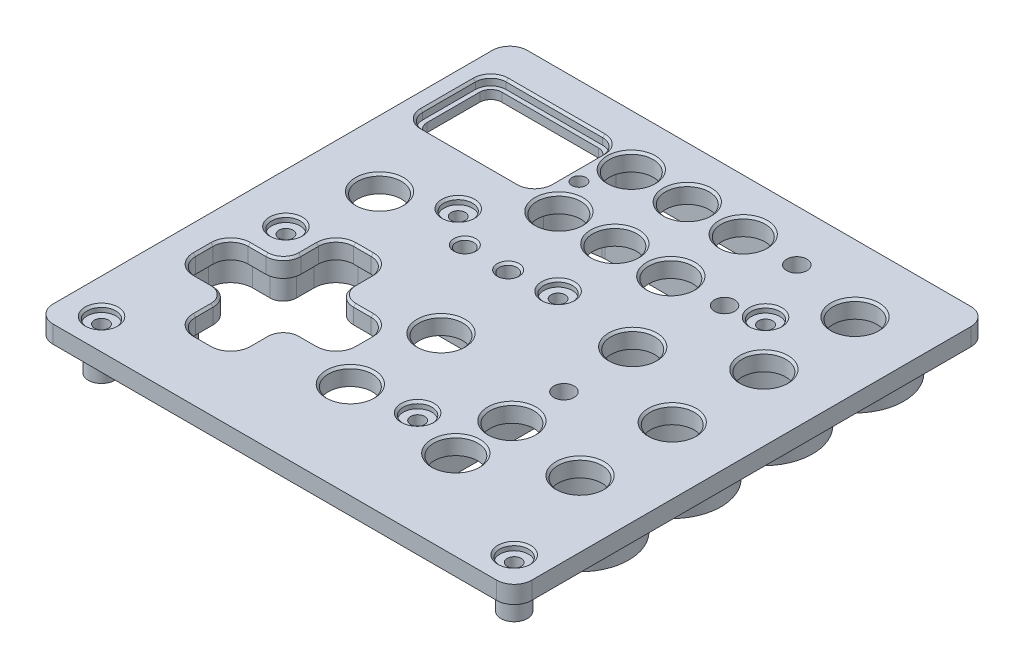
SolidWorks part; units mm, degrees
other "Markup1"
sketch "Sketch10" plane through (-33.0518, -8.9554, -52.6589) normal (-0.1076, -0.9941, -0.0133) x (0.4564, -0.0613, 0.8876)
ref_plane "Front Plane" through (0, 0, 0) normal (0, 0, 1) x (1, 0, 0)
ref_plane "Top Plane" through (0, 0, 0) normal (0, 1, 0) x (1, 0, 0)
ref_plane "Right Plane" through (0, 0, 0) normal (1, 0, 0) x (0, 0, -1)
sketch "Sketch1" plane through (0, 0, 0) normal (0, 1, 0) x (1, 0, 0)
  line L0 (32.6312, 56.5) -> (133.6312, 56.5)
  line L7 (137.6312, -47.5) -> (137.6312, 52.5)
  line L28 (28.6312, 52.5) -> (28.6312, -47.5)
  line L30 (32.6312, -51.5) -> (133.6312, -51.5)
  arc A0 (28.6312, -47.5) -> (32.6312, -51.5) centre (32.6312, -47.5) ccw
  arc A1 (133.6312, -51.5) -> (137.6312, -47.5) centre (133.6312, -47.5) ccw
  arc A2 (137.6312, 52.5) -> (133.6312, 56.5) centre (133.6312, 52.5) ccw
  arc A3 (32.6312, 56.5) -> (28.6312, 52.5) centre (32.6312, 52.5) ccw
  dimension "D2" = 4
extrude "Boss-Extrude1" add sketch "Sketch1" along normal blind 4
sketch "Sketch3" plane through (0, 4, 0) normal (0, 1, 0) x (1, 0, 0)
  line L44 (50.9951, -1.4499) -> (54.9951, -1.4499)
  line L45 (58.9951, -5.4499) -> (58.9951, -9.4499)
  line L46 (62.9951, -13.4499) -> (66.9951, -13.4499)
  line L47 (70.9951, -17.4499) -> (70.9951, -21.4499)
  line L48 (66.9951, -25.4499) -> (62.9951, -25.4499)
  line L49 (58.9951, -29.4499) -> (58.9951, -33.4499)
  line L50 (54.9951, -37.4499) -> (50.9951, -37.4499)
  line L51 (46.9951, -33.4499) -> (46.9951, -29.4499)
  line L52 (42.9951, -25.4499) -> (38.9951, -25.4499)
  line L53 (34.9951, -21.4499) -> (34.9951, -17.4499)
  line L54 (38.9951, -13.4499) -> (42.9951, -13.4499)
  line L55 (46.9951, -9.4499) -> (46.9951, -5.4499)
  circle A2 centre (122.5061, 41.25) radius 5
  circle A3 centre (122.5061, 20.5) radius 5
  circle A4 centre (122.5061, -0.375) radius 5
  circle A5 centre (122.5061, -21.375) radius 5
  circle A6 centre (103.9561, -18.35) radius 5
  circle A7 centre (103.1311, 10) radius 5
  circle A8 centre (78.5811, -9.125) radius 5
  circle A9 centre (78.3063, -29.5) radius 5
  circle A10 centre (43.6312, 11.8249) radius 5
  circle A11 centre (68.0062, 28.3001) radius 5
  circle A12 centre (80.7562, 28.3001) radius 5
  circle A13 centre (93.5062, 28.3001) radius 5
  circle A14 centre (93.5062, 44.8001) radius 5
  circle A15 centre (80.7562, 44.8001) radius 5
  circle A16 centre (68.0062, 44.8001) radius 5
  circle A17 centre (103.9561, -31.125) radius 5
  circle A18 centre (63.8812, 11.0001) radius 2
  circle A19 centre (73.7562, 10.9999) radius 2
  arc A20 (58.9951, -29.4499) -> (62.9951, -25.4499) centre (62.9951, -29.4499) cw
  arc A21 (62.9951, -13.4499) -> (58.9951, -9.4499) centre (62.9951, -9.4499) cw
  arc A22 (46.9951, -9.4499) -> (42.9951, -13.4499) centre (42.9951, -9.4499) cw
  arc A23 (46.9951, -29.4499) -> (42.9951, -25.4499) centre (42.9951, -29.4499) ccw
  arc A24 (70.9951, -17.4499) -> (66.9951, -13.4499) centre (66.9951, -17.4499) ccw
  arc A25 (58.9951, -5.4499) -> (54.9951, -1.4499) centre (54.9951, -5.4499) ccw
  arc A26 (50.9951, -1.4499) -> (46.9951, -5.4499) centre (50.9951, -5.4499) ccw
  arc A27 (38.9951, -13.4499) -> (34.9951, -17.4499) centre (38.9951, -17.4499) ccw
  arc A28 (34.9951, -21.4499) -> (38.9951, -25.4499) centre (38.9951, -21.4499) ccw
  arc A29 (46.9951, -33.4499) -> (50.9951, -37.4499) centre (50.9951, -33.4499) ccw
  arc A30 (54.9951, -37.4499) -> (58.9951, -33.4499) centre (54.9951, -33.4499) ccw
  arc A31 (66.9951, -25.4499) -> (70.9951, -21.4499) centre (66.9951, -21.4499) ccw
  circle A32 centre (105.6344, 44.8749) radius 2.3
  circle A33 centre (105.4147, 28.6249) radius 2.3
  circle A34 centre (104.1313, -6.6735) radius 2.3
  point P54 (58.9951, -13.4499)
extrude "Cut-Extrude2" cut sketch "Sketch3" against normal through all
sketch "Sketch11" plane through (0, 4, 0) normal (0, 1, 0) x (1, 0, 0)
  line L0 (61.4355, 44.8615) -> (61.4355, 32.8615)
  line L4 (32.4355, 32.8615) -> (32.4355, 44.8615)
  line L6 (35.9355, 48.3615) -> (57.9355, 48.3615)
  line L8 (61.4355, 44.8615) -> (61.4355, 32.8615)
  line L9 (57.9355, 29.3615) -> (35.9355, 29.3615)
  line L10 (32.4355, 32.8615) -> (32.4355, 44.8615)
  line L11 (35.9355, 48.3615) -> (57.9355, 48.3615)
  line L13 (57.9355, 29.3615) -> (35.9355, 29.3615)
  arc A0 (57.9355, 29.3615) -> (61.4355, 32.8615) centre (57.9355, 32.8615) ccw
  arc A1 (32.4355, 32.8615) -> (35.9355, 29.3615) centre (35.9355, 32.8615) ccw
  arc A2 (35.9355, 48.3615) -> (32.4355, 44.8615) centre (35.9355, 44.8615) ccw
  arc A3 (61.4355, 44.8615) -> (57.9355, 48.3615) centre (57.9355, 44.8615) ccw
  arc A4 (57.9355, 29.3615) -> (61.4355, 32.8615) centre (57.9355, 32.8615) ccw
  arc A5 (32.4355, 32.8615) -> (35.9355, 29.3615) centre (35.9355, 32.8615) ccw
  arc A6 (35.9355, 48.3615) -> (32.4355, 44.8615) centre (35.9355, 44.8615) ccw
  arc A7 (61.4355, 44.8615) -> (57.9355, 48.3615) centre (57.9355, 44.8615) ccw
extrude "Cut-Extrude8" cut sketch "Sketch11" against normal blind 2
sketch "Sketch12" plane through (0, 2, 0) normal (0, 1, 0) x (1, 0, 0)
  line L4 (57.9355, 47.3615) -> (35.9355, 47.3615)
  line L5 (57.9355, 47.3615) -> (35.9355, 47.3615)
  line L6 (33.4355, 44.8615) -> (33.4355, 32.8615)
  line L7 (33.4355, 44.8615) -> (33.4355, 32.8615)
  line L8 (35.9355, 30.3615) -> (57.9355, 30.3615)
  line L9 (35.9355, 30.3615) -> (57.9355, 30.3615)
  line L10 (60.4355, 32.8615) -> (60.4355, 44.8615)
  line L11 (60.4355, 32.8615) -> (60.4355, 44.8615)
  arc A4 (60.4355, 44.8615) -> (57.9355, 47.3615) centre (57.9355, 44.8615) ccw
  arc A5 (60.4355, 44.8615) -> (57.9355, 47.3615) centre (57.9355, 44.8615) ccw
  arc A6 (35.9355, 47.3615) -> (33.4355, 44.8615) centre (35.9355, 44.8615) ccw
  arc A7 (35.9355, 47.3615) -> (33.4355, 44.8615) centre (35.9355, 44.8615) ccw
  arc A8 (33.4355, 32.8615) -> (35.9355, 30.3615) centre (35.9355, 32.8615) ccw
  arc A9 (33.4355, 32.8615) -> (35.9355, 30.3615) centre (35.9355, 32.8615) ccw
  arc A10 (57.9355, 30.3615) -> (60.4355, 32.8615) centre (57.9355, 32.8615) ccw
  arc A11 (57.9355, 30.3615) -> (60.4355, 32.8615) centre (57.9355, 32.8615) ccw
  dimension "D1" = 1
extrude "Cut-Extrude9" cut sketch "Sketch12" against normal through all
sketch "Sketch13" plane through (0, 0, 0) normal (0, -1, 0) x (1, 0, 0)
  line L0 (133.6312, -52.5) -> (28.6312, -52.5) construction
  line L2 (112.3813, -52.5) -> (112.3813, -45.8325)
  line L4 (61.3813, -52.5) -> (61.3813, -21.5)
  line L5 (68.0062, -22.3001) -> (106.5062, -22.3001)
  line L7 (68.0062, -51.3001) -> (106.5062, -51.3001)
  line L8 (110.5062, -47.3001) -> (110.5062, -42.8001)
  line L10 (68.0062, -38.8001) -> (106.5062, -38.8001)
  line L12 (110.5062, -34.3001) -> (110.5062, -26.3001)
  line L14 (92.0062, -10.073) -> (92.0062, -16.5)
  line L16 (96.9561, 31.125) -> (96.9561, 6.3677)
  line L17 (110.9561, 6.3677) -> (110.9561, 31.125)
  line L18 (94.9561, 31.125) -> (94.9561, 6.3677)
  line L20 (112.9561, 27.1102) -> (112.9561, 31.125)
  line L22 (112.9561, 6.3677) -> (112.9561, 31.125) construction
  line L58 (49.0951, -3.4501) -> (56.6951, -3.4501)
  line L64 (51.4145, 42.1499) -> (49.0951, 42.1499)
  line L65 (42.0951, 35.1499) -> (42.0951, 31.1499)
  line L66 (41.0951, 30.1499) -> (37.0951, 30.1499)
  line L67 (30.0951, 23.1499) -> (30.0951, 15.5499)
  line L68 (37.0951, 8.5499) -> (41.0951, 8.5499)
  line L69 (42.0951, 7.5499) -> (42.0951, 3.5499)
  line L78 (87, 41.2148) -> (87, 1.6203)
  line L80 (87, 41.2148) -> (81.1395, 41.2148)
  line L90 (80.1354, -3.1952) -> (60.3806, -3.1952)
  line L91 (60.3806, -3.1952) -> (56.6951, -3.4501)
  line L92 (81.1395, 41.2148) -> (80.9453, 41.2148)
  line L98 (78.4256, -1.1952) -> (60.3115, -1.1952)
  line L99 (60.3115, -1.1952) -> (56.626, -1.4501)
  line L100 (49.0951, -1.4501) -> (56.626, -1.4501)
  line L101 (44.0951, 7.5499) -> (44.0951, 3.5499)
  line L102 (37.0951, 10.5499) -> (41.0951, 10.5499)
  line L103 (32.0951, 23.1499) -> (32.0951, 15.5499)
  line L104 (41.0951, 28.1499) -> (37.0951, 28.1499)
  line L105 (44.0951, 35.1499) -> (44.0951, 31.1499)
  line L106 (56.6951, 40.1499) -> (49.0951, 40.1499)
  line L112 (88.0062, -20.5) -> (61.3813, -20.5)
  line L113 (61.3813, -20.5) -> (61.3813, -21.5)
  line L114 (110.5062, -34.3001) -> (110.5062, -35.3001)
  line L115 (110.5062, -35.3001) -> (71.526, -35.3001)
  line L117 (72.1395, 36.8974) -> (59.4553, 39.319) construction
  line L118 (81.8089, 36.8974) -> (72.1395, 36.8974) construction
  line L119 (72.3287, 38.8974) -> (60.1904, 41.2148) construction
  line L120 (79.8089, 38.8974) -> (72.3287, 38.8974) construction
  line L122 (85, 39.2148) -> (85, 0.6001) construction
  line L123 (85, 39.2148) -> (81.8089, 39.2148) construction
  line L124 (81.8089, 39.2148) -> (81.8089, 36.8974) construction
  line L126 (81.8089, 39.2148) -> (81.8089, 39.2148) construction
  line L127 (85, 0.6001) -> (78.6937, 0.6001) construction
  line L128 (85, 0.6001) -> (85, 0.6001) construction
  line L129 (85, 4.6001) -> (85, 35.9119)
  line L130 (85, 4.6001) -> (85, 4.3183)
  line L135 (61.3813, -52.5) -> (112.3813, -52.5)
  line L136 (56.6951, 42.1499) -> (49.0951, 42.1499) construction
  line L137 (81.7885, 39.1911) -> (60.1254, 39.1911)
  line L138 (79.8089, 41.2148) -> (79.8089, 38.8974) construction
  line L139 (60.7768, 41.1028) -> (72.9994, 41.1028)
  line L143 (81.1395, 41.2148) -> (79.8089, 41.2148) construction
  line L144 (81.2306, -3.0424) -> (84.0953, -2.2268)
  line L145 (82.4501, -0.032) -> (82.3087, -0.1438)
  line L146 (80.3612, -0.9707) -> (78.9594, -1.1595)
  line L147 (78.6937, -1.1952) -> (60.3115, -1.1952) construction
  line L148 (78.6937, 0.6001) -> (78.6937, -1.1952) construction
  line L149 (85.6449, -1.3999) -> (80.6937, -1.3999) construction
  line L150 (87, -1.3999) -> (85.6449, -1.3999) construction
  line L151 (80.6937, -1.3999) -> (80.6937, -3.1952) construction
  line L152 (80.6937, -3.1952) -> (60.3806, -3.1952) construction
  line L153 (87, 41.2148) -> (87, -1.3999) construction
  line L154 (68.272, -34.8415) -> (70.9104, -35.2525)
  arc A5 (68.0062, -38.8001) -> (62.3939, -46.9221) centre (68.0062, -44.8001) ccw
  arc A7 (68.0062, -51.3001) -> (62.3939, -46.9221) centre (68.0062, -45.5139) cw
  circle A8 centre (122.5061, -41.25) radius 10
  circle A9 centre (122.5061, -20.5) radius 10
  circle A10 centre (122.5061, 0.4031) radius 10
  circle A11 centre (103.1311, -10) radius 10
  circle A12 centre (122.5061, 21.375) radius 10
  arc A15 (130.5136, 13.6804) -> (112.9561, 27.1102) centre (122.506, 21.4034) ccw
  arc A16 (105.5959, 0.8487) -> (101.7697, 1.0416) centre (103.1311, -10) ccw
  arc A20 (130.5579, -7.2744) -> (130.5137, 8.1267) centre (122.5061, 0.4031) ccw
  arc A21 (130.6014, -28.1034) -> (130.5579, -12.795) centre (122.5062, -20.4722) ccw
  arc A25 (112.3813, -45.8325) -> (130.6014, -33.5909) centre (122.5062, -41.2222) ccw
  arc A26 (110.9561, 31.125) -> (96.9561, 31.125) centre (103.9561, 31.125) ccw
  arc A28 (96.9561, 6.3677) -> (97.7122, 3.2032) centre (103.9561, 6.3677) ccw
  arc A29 (112.9561, 31.125) -> (94.9561, 31.125) centre (103.9561, 31.125) ccw
  arc A30 (94.9561, 6.3677) -> (95.8988, 2.3578) centre (103.9561, 6.3677) ccw
  arc A34 (109.8501, 2.5914) -> (110.9561, 6.3677) centre (103.9561, 6.3677) ccw
  arc A35 (94.9561, 6.3677) -> (112.9561, 6.3677) centre (103.9561, 6.3677) ccw construction
  arc A36 (95.1775, -2.2212) -> (92.0062, -10.073) centre (103.1311, -10) ccw
  arc A37 (96.9561, 6.3677) -> (110.9561, 6.3677) centre (103.9561, 6.3677) ccw construction
  arc A76 (42.0951, 3.5499) -> (49.0951, -3.4501) centre (49.0951, 3.5499) ccw
  arc A82 (59.7699, 41.4384) -> (56.6951, 42.1499) centre (56.6951, 35.1499) ccw
  arc A83 (49.0951, 42.1499) -> (42.0951, 35.1499) centre (49.0951, 35.1499) ccw
  arc A84 (41.0951, 30.1499) -> (42.0951, 31.1499) centre (41.0951, 31.1499) ccw
  arc A85 (37.0951, 30.1499) -> (30.0951, 23.1499) centre (37.0951, 23.1499) ccw
  arc A86 (30.0951, 15.5499) -> (37.0951, 8.5499) centre (37.0951, 15.5499) ccw
  arc A87 (42.0951, 7.5499) -> (41.0951, 8.5499) centre (41.0951, 7.5499) ccw
  arc A90 (44.0951, 3.5499) -> (49.0951, -1.4501) centre (49.0951, 3.5499) ccw
  arc A91 (44.0951, 7.5499) -> (41.0951, 10.5499) centre (41.0951, 7.5499) ccw
  arc A92 (32.0951, 15.5499) -> (37.0951, 10.5499) centre (37.0951, 15.5499) ccw
  arc A93 (37.0951, 28.1499) -> (32.0951, 23.1499) centre (37.0951, 23.1499) ccw
  arc A94 (41.0951, 28.1499) -> (44.0951, 31.1499) centre (41.0951, 31.1499) ccw
  arc A95 (49.0951, 40.1499) -> (44.0951, 35.1499) centre (49.0951, 35.1499) ccw
  arc A96 (59.0175, 39.5778) -> (56.6951, 40.1499) centre (56.6951, 35.1499) ccw
  arc A97 (88.0062, -20.5) -> (92.0062, -16.5) centre (88.0062, -16.5) ccw
  arc A98 (130.5136, 13.6804) -> (130.5137, 8.1267) centre (133.3928, 10.9036) ccw
  arc A99 (130.6014, -28.1034) -> (130.6014, -33.5909) centre (133.512, -30.8472) ccw
  arc A100 (130.5579, -7.2744) -> (130.5579, -12.795) centre (133.4528, -10.0347) ccw
  arc A101 (105.5959, 0.8487) -> (109.8501, 2.5914) centre (106.4821, 4.7493) ccw
  arc A102 (101.7697, 1.0416) -> (97.7122, 3.2032) centre (101.2802, 5.0115) cw
  arc A103 (106.5062, -51.3001) -> (110.5062, -47.3001) centre (106.5062, -47.3001) ccw
  arc A104 (106.5062, -38.8001) -> (110.5062, -42.8001) centre (106.5062, -42.8001) cw
  arc A105 (106.5062, -22.3001) -> (110.5062, -26.3001) centre (106.5062, -26.3001) cw
  arc A107 (59.4553, 39.319) -> (56.6951, 40.1499) centre (56.6951, 35.1499) ccw construction
  arc A108 (59.0175, 39.5778) -> (60.1254, 39.1911) centre (60.8755, 43.1201) ccw
  arc A109 (60.1904, 41.2148) -> (56.6951, 42.1499) centre (56.6951, 35.1499) ccw construction
  arc A110 (59.7699, 41.4384) -> (60.7768, 41.1028) centre (61.527, 45.0318) ccw
  arc A112 (95.8988, 2.3578) -> (95.1775, -2.2212) centre (92.3178, 0.5756) cw
  arc A113 (85, 35.9119) -> (81.7885, 39.1911) centre (83.5458, 37.6999) ccw
  arc A115 (83.8131, 0.6711) -> (85.1693, 3.167) centre (83.2539, 2.5914) ccw
  arc A116 (85.1693, 3.167) -> (85, 4.3183) centre (89, 4.3183) cw
  arc A117 (56.6951, 42.1499) -> (55.6799, 42.0189) centre (56.6951, 38.1499) ccw
  arc A118 (51.4145, 42.1499) -> (52.8417, 41.8866) centre (51.4145, 38.1499) cw
  arc A119 (52.8417, 41.8866) -> (55.6799, 42.0189) centre (54.1092, 45.2051) ccw
  arc A120 (74.7448, 40.7019) -> (72.9994, 41.1028) centre (72.9994, 37.1028) ccw
  arc A121 (74.7448, 40.7019) -> (79.0991, 40.7632) centre (76.8609, 45.0653) ccw
  arc A122 (80.9453, 41.2148) -> (79.0991, 40.7632) centre (80.9453, 37.2148) ccw
  arc A123 (78.9594, -1.1595) -> (78.4256, -1.1952) centre (78.4256, 2.8048) cw
  arc A124 (82.3087, -0.1438) -> (80.3612, -0.9707) centre (79.8274, 2.9935) cw
  arc A125 (83.8131, 0.6711) -> (82.4501, -0.032) centre (84.9315, -3.1693) ccw
  arc A126 (81.2306, -3.0424) -> (80.1354, -3.1952) centre (80.1354, 0.8048) cw
  arc A127 (87, 1.6203) -> (84.0953, -2.2268) centre (83, 1.6203) cw
  arc A128 (67.7993, -34.7964) -> (62.3939, -30.4221) centre (68.0062, -29.0139) cw
  arc A129 (68.0062, -22.3001) -> (62.3939, -30.4221) centre (68.0062, -28.3001) ccw
  arc A130 (71.526, -35.3001) -> (70.9104, -35.2525) centre (71.526, -31.3001) cw
  arc A131 (68.272, -34.8415) -> (67.7993, -34.7964) centre (67.6564, -38.7939) ccw
  point P139 (56.6951, 3.5499)
  point P140 (63.6951, 3.5499)
  point P144 (68.6951, 8.5499)
  point P145 (68.6951, 15.5499)
  point P146 (75.6951, 15.5499)
  point P153 (63.6951, 35.1499)
  dimension "D3" = 4
  dimension "D1" = 4
  dimension "D4" = 4
  dimension "D5" = 4
  dimension "D6" = 4
  dimension "D7" = 4
  dimension "D8" = 4
  dimension "D9" = 4
  dimension "D10" = 4
  dimension "D11" = 4
  dimension "D12" = 4
  dimension "D13" = 4
  dimension "D14" = 4
  dimension "D15" = 4
  dimension "D16" = 4
  dimension "D17" = 4
  dimension "D2" = 51
extrude "Boss-Extrude2" add sketch "Sketch13" along normal blind 7.1
sketch "Sketch14" plane through (0, -7.1, 0) normal (0, -1, 0) x (1, 0, 0)
  line L0 (110.9561, 31.125) -> (110.9561, 40.2144)
  line L5 (110.9561, 40.2144) -> (106.9561, 40.2144)
  line L7 (106.9561, 31.125) -> (110.9561, 31.125)
  line L8 (106.9561, 31.125) -> (96.9561, 31.125)
  line L9 (96.9561, 31.125) -> (96.9561, 40.2144)
  line L10 (96.9561, 40.2144) -> (106.9561, 40.2144)
extrude "Cut-Extrude10" cut sketch "Sketch14" against normal blind 1.5
sketch "Sketch8" plane through (0, 4, 0) normal (0, -1, 0) x (-1, 0, 0)
  circle A0 centre (-36.6312, -44.5) radius 1.6
  circle A1 centre (-91.6312, -27.5) radius 1.6
  circle A2 centre (-39.8812, -5.75) radius 1.6
  circle A3 centre (-56.0062, 17.375) radius 1.6
  circle A4 centre (-64.3812, 36.5) radius 1.6
  circle A5 centre (-83.6312, 12.5) radius 1.6
  circle A6 centre (-112.3812, 31) radius 1.6
  circle A7 centre (-130.6312, -44.5) radius 1.6
extrude "Cut-Extrude7" cut sketch "Sketch8" along normal through all
sketch "Sketch16" plane through (0, 0, 0) normal (0, -1, 0) x (1, 0, 0)
  line L1 (37.0951, 8.5499) -> (41.0951, 8.5499) construction
  line L3 (40.9586, 8.5499) -> (41.0951, 8.5499)
  line L4 (87, 1.6203) -> (87, 41.2148) construction
  line L5 (94.9561, 31.125) -> (94.9561, 6.3677) construction
  line L6 (87, 24.5) -> (87, 30.5)
  line L7 (94.9561, 30.5) -> (94.9561, 24.5)
  line L8 (91.6312, 24.5) -> (87, 24.5)
  line L9 (91.6312, 30.5) -> (87, 30.5)
  line L10 (91.6312, 30.5) -> (94.9561, 30.5)
  line L11 (91.6312, 24.5) -> (94.9561, 24.5)
  circle A0 centre (36.6312, 44.5) radius 3
  arc A1 (40.9586, 8.5499) -> (42.0601, 7.8121) centre (39.8812, 5.75) ccw
  circle A2 centre (56.0062, -17.375) radius 3
  circle A4 centre (130.6312, 44.5) radius 3
  circle A5 centre (83.6312, -12.5) radius 3
  arc A6 (42.0951, 7.5499) -> (41.0951, 8.5499) centre (41.0951, 7.5499) ccw construction
  arc A7 (42.0601, 7.8121) -> (41.0951, 8.5499) centre (41.0951, 7.5499) ccw
fillet "Fillet1" radius 4 1 edges at (110.5062, -3.55, -35.3001)
fillet "Fillet2" radius 4 1 edges at (112.9561, -3.55, 27.1102)
fillet "Fillet5" radius 4 1 edges at (112.3813, -3.55, -45.8325)
sketch "Sketch15" plane through (0, 4, 0) normal (0, 1, 0) x (1, 0, 0)
  circle A0 centre (56.0062, 17.375) radius 3.25
  circle A1 centre (39.8812, -5.75) radius 3.25
  circle A2 centre (36.6312, -44.5) radius 3.25
  circle A3 centre (91.6312, -27.5) radius 3.25
  circle A4 centre (130.6312, -44.5) radius 3.25
  circle A5 centre (112.3812, 31) radius 3.25
  circle A6 centre (83.6312, 12.5) radius 3.25
extrude "Cut-Extrude11" cut sketch "Sketch15" against normal blind 1.5
chamfer "Chamfer1" distance 0.5 angle 45 57 edges at (93.5062, 4, -39.8001) (80.7562, 4, -39.8001) (68.0062, 4, -39.8001) (63.8812, 4, -9.0001) (73.7562, 4, -8.9999) (83.6312, 4, -9.25) (56.0062, 4, -14.125) (43.6312, 4, -6.8249) (39.8812, 4, 9) (36.6312, 4, 47.75) (52.9951, 4, 37.4499) (46.9951, 4, 31.4499) (45.8235, 4, 26.6215) (40.9951, 4, 25.4499) (34.9951, 4, 19.4499) (40.9951, 4, 13.4499) (45.8235, 4, 12.2783) (46.9951, 4, 7.4499) (52.9951, 4, 1.4499) (58.9951, 4, 31.4499) (58.9951, 4, 7.4499) (60.1667, 4, 26.6215) (60.1667, 4, 12.2783) (64.9951, 4, 25.4499) (70.9951, 4, 19.4499) (64.9951, 4, 13.4499) (78.5811, 4, 14.125) (78.3063, 4, 34.5) (130.6312, 4, 47.75) (91.6312, 4, 30.75) (103.9561, 4, 36.125) (103.9561, 4, 23.35) (122.5061, 4, 26.375) (122.5061, 4, 5.375) (103.1311, 4, -5) (122.5061, 4, -15.5) (112.3812, 4, -27.75) (93.5062, 4, -23.3001) (80.7562, 4, -23.3001) (68.0062, 4, -23.3001) (32.4355, 4, -38.8615) (61.4355, 4, -38.8615) (46.9355, 4, -29.3615) (60.4103, 4, -30.3866) (33.4606, 4, -30.3866) (60.4103, 4, -47.3364) (33.4606, 4, -47.3364) (46.9355, 4, -48.3615) (122.5061, 4, -36.25) (36.1667, 4, 24.2783) (48.1667, 4, 36.2783) (36.1667, 4, 14.6215) (57.8235, 4, 36.2783) (48.1667, 4, 2.6215) (69.8235, 4, 24.2783) (57.8235, 4, 2.6215) (69.8235, 4, 14.6215)
fillet "Fillet10" radius 3 1 edges at (87, -3.55, 41.2148)
extrude "Boss-Extrude4" add sketch "Sketch16" along normal up to surface (7.1 mm away) up to face at (112.3812, -7.1, -32.6)
sketch "Sketch17" plane through (0, 0, 0) normal (0, 1, 0) x (1, 0, 0)
  circle A0 centre (36.6312, -44.5) radius 1.6
  circle A1 centre (39.8812, -5.75) radius 1.6
  circle A2 centre (56.0062, 17.375) radius 1.6
  circle A3 centre (83.6312, 12.5) radius 1.6
  circle A4 centre (91.6312, -27.5) radius 1.6
  circle A6 centre (130.6312, -44.5) radius 1.6
extrude "Cut-Extrude12" cut sketch "Sketch17" against normal through all
fillet "Fillet13" radius 2 9 edges at (94.9561, -3.55, 30.5) (87, -3.55, 30.5) (94.9561, -3.55, 24.5) (87, -3.55, 24.5) (38.8039, -3.55, 8.5499) (42.0951, -3.55, 3.7255) (61.3813, -3.55, -20.5) (112.3813, -3.55, -52.5) (61.3813, -3.55, -52.5)
